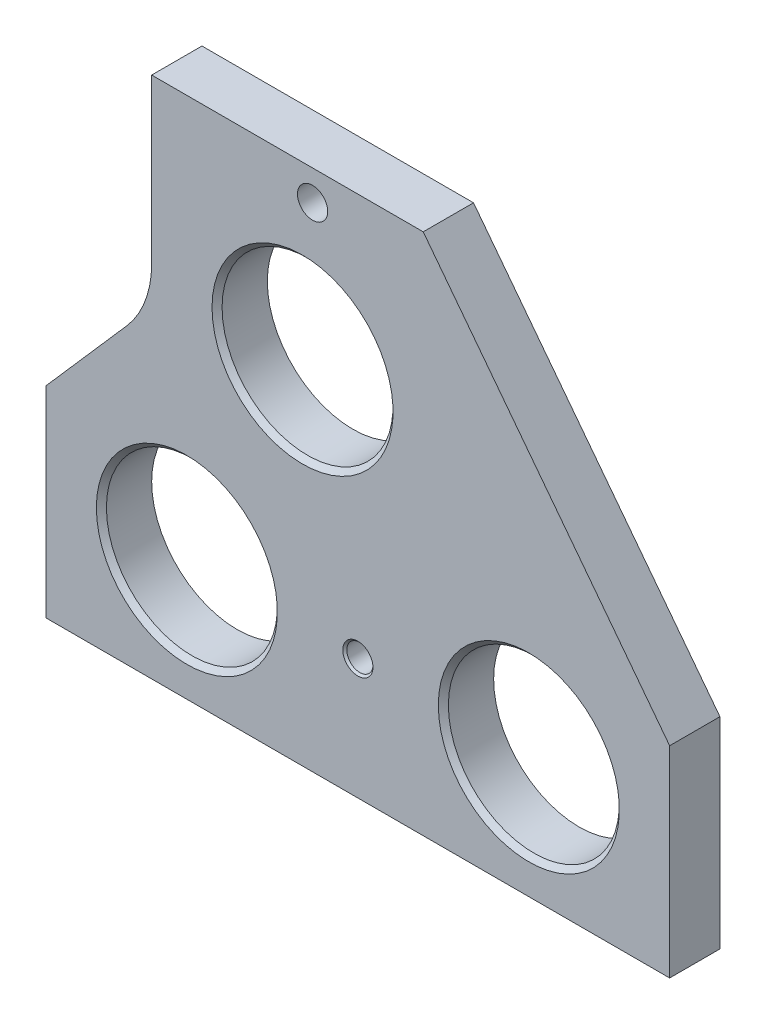
SolidWorks part; units mm, degrees
material "Stop 1060"
ref_plane "Płaszczyzna przednia" through (0, 0, 0) normal (0, 0, 1) x (1, 0, 0)
ref_plane "Płaszczyzna górna" through (0, 0, 0) normal (0, 1, 0) x (1, 0, 0)
ref_plane "Płaszczyzna prawa" through (0, 0, 0) normal (1, 0, 0) x (0, 0, -1)
sketch "Szkic1" plane through (0, 0, 0) normal (0, 0, 1) x (1, 0, 0)
  line L0 (-14, -12) -> (-14, 8)
  line L1 (-3.5, 40) -> (23.5, 40)
  line L2 (48, 8) -> (48, -12)
  line L3 (48, -12) -> (-14, -12)
  line L4 (-3.5, 40) -> (-3.5, 20)
  line L6 (-14, 8) -> (-3.5, 20)
  line L7 (23.5, 40) -> (48, 8)
  circle A0 centre (0, 0) radius 8.5
  circle A1 centre (34, 0) radius 8.5
  circle A2 centre (11.5, 23) radius 8.5
  circle A3 centre (12.5, 37) radius 1.5
  circle A4 centre (17, 0) radius 1.3
  dimension "D1" = 17
  dimension "D2" = 17
  dimension "D3" = 17
  dimension "D4" = 34
  dimension "D5" = 23
  dimension "D6" = 11.5
  dimension "D8" = 14
  dimension "D9" = 14
  dimension "D10" = 3
  dimension "D11" = 12
  dimension "D17" = 3
  dimension "D18" = 16
  dimension "D19" = 3
  dimension "D20" = 17
  dimension "D21" = 23
  dimension "3" = 2.6
  dimension "D7" = 12
  dimension "D12" = 20
  dimension "D13" = 27
  dimension "D14" = 20
  dimension "D15" = 20
  dimension "D16" = 24.5
extrude "Dodanie-wyciągnięcie1" add sketch "Szkic1" along normal blind 5
chamfer "Sfazowanie2" distance 0.5 angle 45 3 edges at (42.5, 0, 5) (20, 23, 5) (8.5, 0, 5)
chamfer "Sfazowanie3" distance 0.2 angle 45 2 edges at (18.3, 0, 0) (18.3, 0, 5)
fillet "Zaokrąglenie1" radius 10 1 edges at (-3.5, 20, 2.5)
